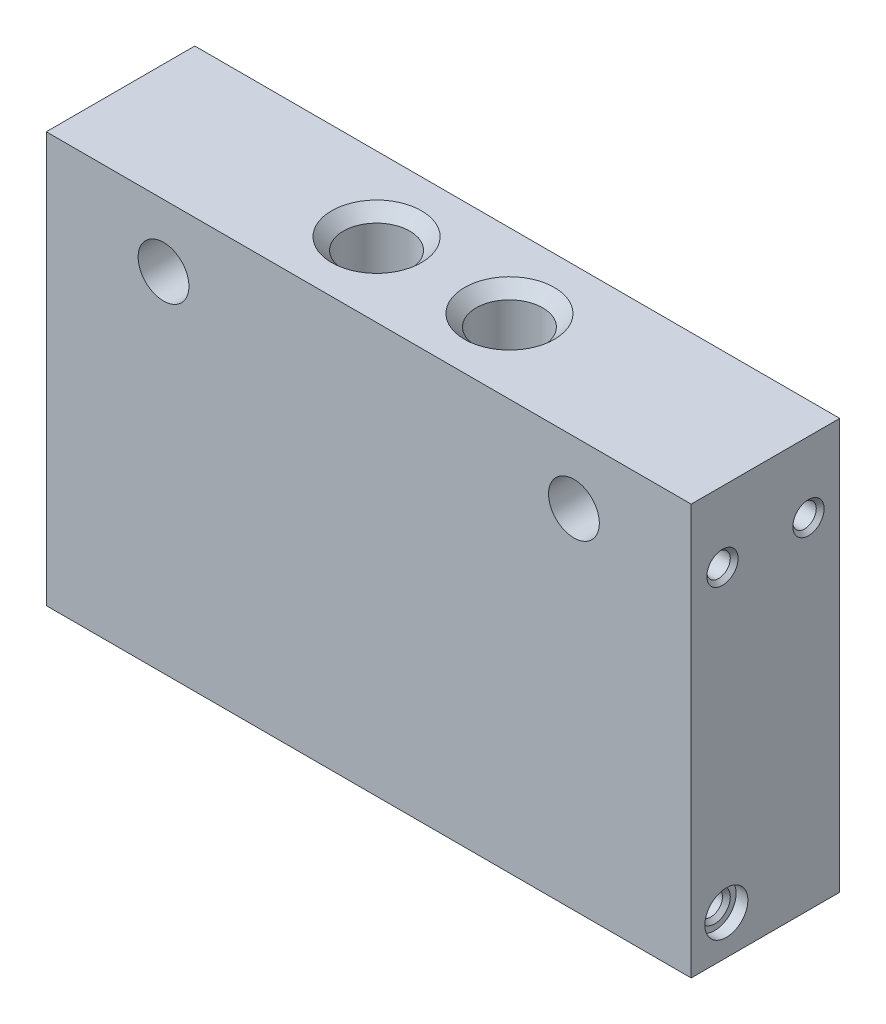
SolidWorks part; units mm, degrees
ref_plane "Front Plane" through (0, 0, 0) normal (0, 0, 1) x (1, 0, 0)
ref_plane "Top Plane" through (0, 0, 0) normal (0, 1, 0) x (1, 0, 0)
ref_plane "Right Plane" through (0, 0, 0) normal (1, 0, 0) x (0, 0, -1)
sketch "Sketch1" plane through (0, 0, 0) normal (0, 1, 0) x (1, 0, 0)
  line L0 (0, 0) -> (41.91, 0)
  line L1 (41.91, 9.652) -> (0, 9.652)
  line L2 (0, 9.652) -> (0, 0)
  line L3 (41.91, 9.652) -> (41.91, 0)
  dimension "D1" = 41.91
  dimension "D2" = 9.652
extrude "Boss-Extrude1" add sketch "Sketch1" along normal blind 26.67
sketch "Sketch2" plane through (0, 0, 0) normal (0, 0, 1) x (1, 0, 0)
  line L0 (41.91, 26.67) -> (41.91, 0) construction
  line L1 (0, 26.67) -> (41.91, 26.67) construction
  line L2 (20.955, 26.67) -> (20.955, 0) construction
  line L3 (0, 0) -> (41.91, 0) construction
  circle A0 centre (34.29, 22.606) radius 1.651
  circle A1 centre (7.62, 22.606) radius 1.651
  dimension "D1" = 3.302
  dimension "D2" = 7.62
  dimension "D3" = 4.064
extrude "Cut-Extrude1" cut sketch "Sketch2" against normal through all
sketch "Sketch3" plane through (0, 26.67, 0) normal (0, 1, 0) x (1, 0, 0)
  line L0 (41.91, 0) -> (41.91, 9.652) construction
  line L1 (41.91, 9.652) -> (0, 9.652) construction
  line L2 (25.273, 4.826) -> (25.273, 9.652) construction
  line L3 (25.273, 4.826) -> (25.273, 0) construction
  line L4 (0, 0) -> (41.91, 0) construction
  line L5 (20.955, 9.652) -> (20.955, 0) construction
  circle A0 centre (25.273, 4.826) radius 2.159
  circle A1 centre (16.637, 4.826) radius 2.159
  dimension "D1" = 16.637
  dimension "D2" = 4.318
extrude "Cut-Extrude2" cut sketch "Sketch3" against normal blind 6.35
chamfer "Chamfer5" distance 0.762 angle 45 2 edges at (16.637, 26.67, -6.985) (25.273, 26.67, -2.667)
sketch "Sketch5" plane through (0, 0, 0) normal (0, -1, 0) x (-1, 0, 0)
  line L0 (-41.91, 0) -> (-41.91, 9.652) construction
  line L1 (-33.401, 0) -> (-33.401, 4.826) construction
  line L2 (0, 0) -> (-41.91, 0) construction
  line L3 (-33.401, 4.826) -> (-33.401, 9.652) construction
  line L4 (-41.91, 9.652) -> (0, 9.652) construction
  line L5 (-20.955, 9.652) -> (-20.955, 0) construction
  circle A0 centre (-33.401, 4.826) radius 2.159
  circle A1 centre (-8.509, 4.826) radius 2.159
  circle A2 centre (-20.955, 4.826) radius 2.159
  point P2 (-41.91, 4.826)
  dimension "D1" = 4.318
  dimension "D3" = 4.318
  dimension "D2" = 8.509
extrude "Cut-Extrude4" cut sketch "Sketch5" against normal blind 5.08
sketch "Sketch6" plane through (0, 0, 0) normal (0, -1, 0) x (-1, 0, 0)
  circle A0 centre (-33.401, 4.826) radius 2.921
  circle A1 centre (-20.955, 4.826) radius 2.921
  circle A2 centre (-8.509, 4.826) radius 2.921
  dimension "D1" = 5.842
extrude "Cut-Extrude5" cut sketch "Sketch6" against normal blind 0.762
chamfer "Chamfer2" distance 0.762 angle 45 3 edges at (8.509, 0.762, -7.747) (20.955, 0.762, -7.747) (33.401, 0.762, -7.747)
sketch "Sketch7" plane through (41.91, 0, 0) normal (1, 0, 0) x (0, 0, -1)
  line L0 (0, 0) -> (9.652, 0) construction
  line L3 (0, 26.67) -> (0, 0) construction
  circle A0 centre (2.286, 2.54) radius 0.762
  dimension "D3" = 1.524
  dimension "D1" = 2.54
  dimension "D2" = 2.286
extrude "Cut-Extrude6" cut sketch "Sketch7" against normal blind 5.334 contours A0
sketch "Sketch9" plane through (41.91, 0, 0) normal (1, 0, 0) x (0, 0, -1)
  circle A0 centre (2.286, 2.54) radius 1.016
  dimension "D1" = 2.032
extrude "Cut-Extrude7" cut sketch "Sketch9" against normal blind 1.27 contours A0
sketch "Sketch10" plane through (41.91, 0, 0) normal (1, 0, 0) x (0, 0, -1)
  circle A0 centre (2.286, 2.54) radius 1.397
  dimension "D1" = 2.794
extrude "Cut-Extrude8" cut sketch "Sketch10" against normal blind 0.762 contours A0
chamfer "Chamfer3" distance 0.508 angle 45 1 edges at (40.64, 2.54, -3.302)
sketch "Sketch11" plane through (0, 0, 0) normal (0, 0, 1) x (1, 0, 0)
  line L0 (20.955, 26.67) -> (20.955, 0) construction
  line L1 (0, 26.67) -> (41.91, 26.67) construction
  line L2 (0, 0) -> (41.91, 0) construction
ref_plane "Plane1" through (20.955, 0, 0) normal (-1, 0, 0) x (0, -1, 0)
mirror "Mirror2" about plane through (20.955, 0, 0) normal (-1, 0, 0) of "Chamfer3", "Cut-Extrude6", "Cut-Extrude8", "Cut-Extrude7"
sketch "Sketch12" plane through (0, 0, 0) normal (-1, 0, 0) x (0, 0, 1)
  line L0 (-9.652, 26.67) -> (0, 26.67) construction
  line L3 (0, 26.67) -> (0, 0) construction
  line L4 (-4.826, 26.67) -> (-4.826, 12.431) construction
  circle A0 centre (-2.032, 22.098) radius 0.762
  circle A1 centre (-7.62, 22.098) radius 0.762
  dimension "D1" = 1.524
  dimension "D2" = 4.572
  dimension "D3" = 2.032
extrude "Cut-Extrude9" cut sketch "Sketch12" against normal blind 4.572
sketch "Sketch14" plane through (0, 0, 0) normal (-1, 0, 0) x (0, 0, 1)
  circle A0 centre (-7.62, 22.098) radius 1.016
  circle A1 centre (-2.032, 22.098) radius 1.016
  dimension "D1" = 2.032
extrude "Cut-Extrude10" cut sketch "Sketch14" against normal blind 0.254
chamfer "Chamfer4" distance 0.254 angle 45 2 edges at (0.254, 22.098, -6.604) (0.254, 22.098, -1.016)
mirror "Mirror3" about plane through (20.955, 0, 0) normal (-1, 0, 0) of "Chamfer4", "Cut-Extrude10", "Cut-Extrude9"
